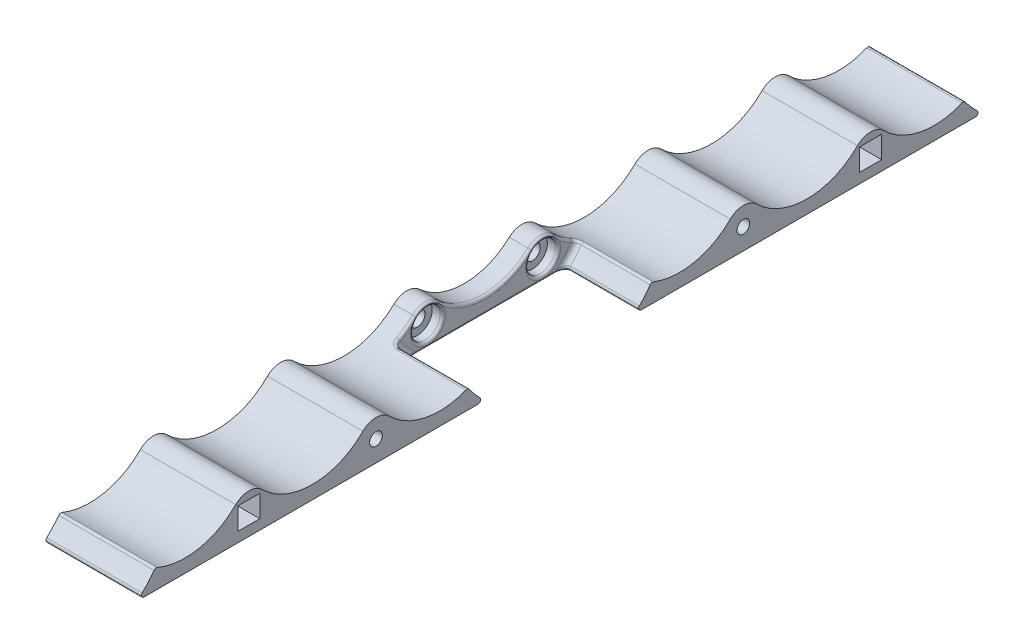
SolidWorks part; units mm, degrees
ref_plane "Front Plane" through (0, 0, 0) normal (0, 0, 1) x (1, 0, 0)
ref_plane "Top Plane" through (0, 0, 0) normal (0, 1, 0) x (1, 0, 0)
ref_plane "Right Plane" through (0, 0, 0) normal (1, 0, 0) x (0, 0, -1)
sketch "Sketch1" plane through (0, 0, 0) normal (1, 0, 0) x (0, 0, -1)
  line L0 (-126.5656, -24.6062) -> (126.5656, -24.6062)
  arc A0 (126.5656, -24.6062) -> (121.1052, -18.6881) centre (148.1579, 0.7938) cw
  arc A1 (-126.5656, -24.6062) -> (-121.1052, -18.6881) centre (-148.1579, 0.7937) ccw
  circle A2 centre (-93.1246, -18.3223) radius 5.5562 construction
  arc A3 (-93.1246, -9.0244) -> (-55.0246, -9.0244) centre (-74.0746, 0.7938) ccw construction
  circle A4 centre (-55.0246, -18.3223) radius 5.5562 construction
  arc A5 (-55.0246, -9.0244) -> (-17.2998, -9.7206) centre (-35.9746, 0.7938) ccw construction
  circle A6 centre (-17.2515, -18.6426) radius 5.5562 construction
  arc A7 (-17.2998, -9.7206) -> (17.2998, -9.7206) centre (0, 0) ccw construction
  circle A8 centre (17.2515, -18.6426) radius 5.5562 construction
  arc A9 (17.2998, -9.7206) -> (55.0246, -9.0244) centre (35.9746, 0.7937) ccw construction
  circle A10 centre (55.0246, -18.3223) radius 5.5562 construction
  circle A11 centre (93.1246, -18.3223) radius 5.5562 construction
  arc A12 (93.1246, -9.0244) -> (131.0767, -9.3061) centre (112.1746, 0.7937) ccw construction
  arc A13 (55.0246, -9.0244) -> (93.1246, -9.0244) centre (74.0746, 0.7937) ccw construction
  arc A14 (-89.2025, -14.3866) -> (-97.0466, -14.3866) centre (-93.1246, -18.3223) ccw
  arc A15 (-89.2025, -14.3866) -> (-58.9466, -14.3866) centre (-74.0746, 0.7938) ccw
  arc A16 (-51.1025, -14.3866) -> (-58.9466, -14.3866) centre (-55.0246, -18.3223) ccw
  arc A17 (-51.1025, -14.3866) -> (-21.1062, -14.641) centre (-35.9746, 0.7938) ccw
  arc A18 (-13.4777, -14.5645) -> (-21.1062, -14.641) centre (-17.2515, -18.6426) ccw
  arc A19 (-13.4777, -14.5645) -> (13.4777, -14.5645) centre (0, 0) ccw
  arc A20 (21.1062, -14.641) -> (13.4777, -14.5645) centre (17.2515, -18.6426) ccw
  arc A21 (21.1062, -14.641) -> (51.1025, -14.3866) centre (35.9746, 0.7937) ccw
  arc A22 (58.9466, -14.3866) -> (51.1025, -14.3866) centre (55.0246, -18.3223) ccw
  arc A23 (97.0466, -14.3866) -> (89.2025, -14.3866) centre (93.1246, -18.3223) ccw
  arc A24 (97.0466, -14.3866) -> (121.1052, -18.6881) centre (112.1746, 0.7937) ccw
  arc A25 (58.9466, -14.3866) -> (89.2025, -14.3866) centre (74.0746, 0.7937) ccw
  arc A26 (-131.0767, -9.3061) -> (-93.1246, -9.0244) centre (-112.1746, 0.7937) ccw construction
  arc A27 (-121.1052, -18.6881) -> (-97.0466, -14.3866) centre (-112.1746, 0.7937) ccw
  arc A28 (-121.4778, 20.7828) -> (-125.0548, 24.8278) centre (-148.1579, 0.7937) ccw construction
  point P3 (0, -24.6062)
  point P9 (121.3317, 38.8336)
  point P12 (-100.9412, 31.521)
  point P13 (0, 0)
  point P14 (0, 0)
  point P40 (-112.0155, -20.6369)
  dimension "D1" = 24.6062
extrude "Boss-Extrude1" add sketch "Sketch1" along normal up to surface (28.575 mm away)
sketch "Sketch2" plane through (28.575, 0, 0) normal (1, 0, 0) x (0, 0, -1)
  circle A0 centre (0, 0) radius 33.3375
  arc A1 (-22.2685, 24.8093) -> (-26.2326, 20.5727) centre (0, 0) ccw construction
extrude "Cut-Extrude1" cut sketch "Sketch2" against normal up to surface (22.225 mm away)
sketch "Sketch3" plane through (28.575, 0, 0) normal (1, 0, 0) x (0, 0, -1)
  line L9 (-89.8226, -15.0203) -> (-96.4266, -15.0203)
  line L10 (-89.8226, -21.6243) -> (-89.8226, -15.0203)
  line L11 (-96.4266, -21.6243) -> (-89.8226, -21.6243)
  line L12 (-96.4266, -15.0203) -> (-96.4266, -21.6243)
  line L13 (-89.8226, -15.0203) -> (-96.4266, -15.0203)
  line L14 (-89.8226, -21.6243) -> (-89.8226, -15.0203)
  line L15 (-96.4266, -21.6243) -> (-89.8226, -21.6243)
  line L16 (-96.4266, -15.0203) -> (-96.4266, -21.6243)
  line L22 (89.8226, -21.6243) -> (96.4266, -21.6243)
  line L23 (96.4266, -21.6243) -> (96.4266, -15.0203)
  line L24 (96.4266, -15.0203) -> (89.8226, -15.0203)
  line L25 (89.8226, -15.0203) -> (89.8226, -21.6243)
  line L26 (89.8226, -21.6243) -> (96.4266, -21.6243)
  line L27 (96.4266, -21.6243) -> (96.4266, -15.0203)
  line L28 (96.4266, -15.0203) -> (89.8226, -15.0203)
  line L29 (89.8226, -15.0203) -> (89.8226, -21.6243)
  dimension "D1" = 0.127
  dimension "D2" = 0.127
extrude "Cut-Extrude2" cut sketch "Sketch3" against normal through all
sketch "Sketch4" plane through (28.575, 0, 0) normal (1, 0, 0) x (0, 0, -1)
  point P0 (-55.0246, -18.3223)
  point P3 (55.0246, -18.3223)
  point P11 (0, 0)
hole_wizard "#8 Clearance Hole1" positions "Sketch4" profile "Sketch5" hole size "#8" standard "ANSI Inch" end condition up to next
sketch "Sketch5" plane through (28.575, -18.3223, 55.0246) normal (0, 1, 0) x (0, 0, -1)
  line L0 (0, 0) -> (0, 28.575)
  line L1 (0, 28.575) -> (1.905, 28.575)
  line L2 (1.905, 28.575) -> (1.905, 0)
  line L5 (1.905, 0) -> (0, 0)
  line L11 (0, -6.35) -> (0, 107.95) construction
  dimension "Thru Hole Dia." = 3.81
  dimension "Thru Hole Depth" = 28.575
sketch "Sketch6" plane through (6.35, 0, 0) normal (1, 0, 0) x (0, 0, -1)
  circle A0 centre (-17.2515, -18.6426) radius 4.445
  circle A1 centre (17.2515, -18.6426) radius 4.445
  dimension "D1" = 8.89
extrude "Cut-Extrude3" cut sketch "Sketch6" against normal blind 3.175
sketch "Sketch7" plane through (3.175, 0, 0) normal (1, 0, 0) x (0, 0, -1)
  point P0 (-17.2515, -18.6426)
  point P3 (17.2515, -18.6426)
hole_wizard "#8 Clearance Hole2" positions "Sketch7" profile "Sketch8" hole size "#8" standard "ANSI Inch" end condition up to next
sketch "Sketch8" plane through (3.175, -18.6426, 17.2515) normal (0, 1, 0) x (0, 0, -1)
  line L0 (0, 0) -> (0, 3.175)
  line L1 (0, 3.175) -> (2.286, 3.175)
  line L2 (2.286, 3.175) -> (2.286, 0)
  line L5 (2.286, 0) -> (0, 0)
  line L11 (0, -6.35) -> (0, 107.95) construction
  dimension "Thru Hole Dia." = 4.572
  dimension "Thru Hole Depth" = 3.175
fillet "Fillet1" radius 1.5875 2 edges at (6.35, -21.8856, -25.1478) (6.35, -21.8856, 25.1478)
fillet "Fillet2" radius 0.7937 20 edges at (18.2563, -18.8803, -27.4758) (6.7035, -18.6353, -26.9296) (6.35, -16.5891, -23.4393) (6.35, -13.0866, -17.3072) (18.2563, -18.8803, 27.4758) (6.9586, -18.7415, 27.1614) (6.35, -16.5891, 23.4393) (6.35, -13.0866, 17.3072) (18.2562, -24.6062, 22.4927) (6.8874, -24.6062, 21.9001) (18.2562, -24.6062, -22.4927) (7.1838, -24.6062, -22.2096) (6.35, -18.6426, -21.6965) (6.35, -18.6426, 12.8065) (6.35, -19.8438, 0) (6.35, -24.6062, 0) (14.2875, -24.6062, -126.5656) (14.2875, -18.6881, -121.1052) (14.2875, -24.6062, 126.5656) (14.2875, -18.6881, 121.1052)
